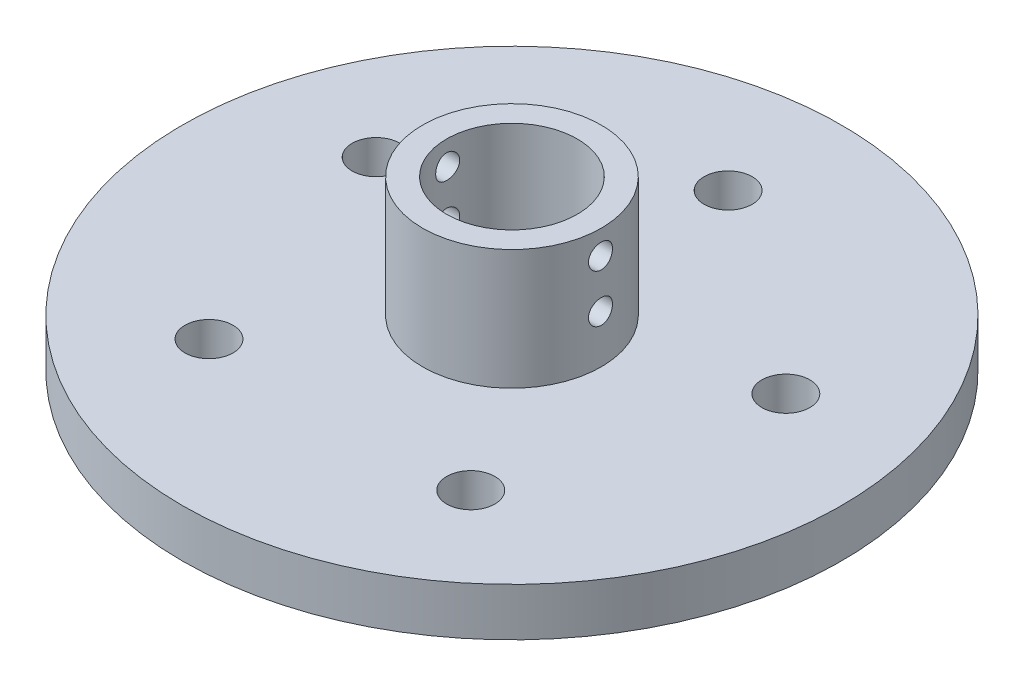
SolidWorks part; units mm, degrees
material "Delrin 2700 NC010, Low Viscosity Acetal Copolymer (SS)"
ref_plane "Front Plane" through (0, 0, 0) normal (0, 0, 1) x (1, 0, 0)
ref_plane "Top Plane" through (0, 0, 0) normal (0, 1, 0) x (1, 0, 0)
ref_plane "Right Plane" through (0, 0, 0) normal (1, 0, 0) x (0, 0, -1)
sketch "Sketch1" plane through (0, 0, 0) normal (0, 0, 1) x (1, 0, 0)
  line L0 (0, 7.8095) -> (0, 0) construction
  line L1 (0, 0) -> (17.272, 0) construction
  line L3 (17.272, 0) -> (87.122, 0)
  line L4 (17.272, 0) -> (17.272, 12.7)
  line L5 (17.272, 12.7) -> (87.122, 12.7)
  line L6 (87.122, 0) -> (87.122, 12.7)
  line L7 (17.272, 12.7) -> (23.622, 12.7)
  line L8 (17.272, 12.7) -> (17.272, 44.45)
  line L9 (17.272, 44.45) -> (23.622, 44.45)
  line L10 (23.622, 12.7) -> (23.622, 44.45)
  dimension "D1" = 17.272
  dimension "D2" = 12.7
  dimension "D3" = 6.35
  dimension "D4" = 31.75
  dimension "5.5" = 69.85
revolve "Revolve1" add sketch "Sketch1" angle 360 about L0 region at (52.197, 6.35, 0) region at (20.447, 28.575, 0)
sketch "Sketch2" plane through (0, 12.7, 0) normal (0, 1, 0) x (1, 0, 0)
  line L0 (0, 57.15) -> (54.1556, 18.2562) construction
  line L1 (54.1556, 18.2562) -> (34.5994, -45.4863) construction
  line L2 (34.5994, -45.4863) -> (-34.5994, -45.4863) construction
  line L3 (-34.5994, -45.4863) -> (-54.1556, 18.2562) construction
  line L4 (-54.1556, 18.2562) -> (0, 57.15) construction
  circle A0 centre (0, 0) radius 57.15 construction
  point P3 (-54.1556, 18.2562)
  point P4 (0, 57.15)
  point P5 (54.1556, 18.2562)
  point P6 (-34.5994, -45.4863)
  point P7 (34.5994, -45.4863)
  dimension "D1" = 114.3
  dimension "D2" = 66.675
hole_wizard "1/2-20 Tapped Hole1" positions "Sketch3" profile "Sketch4" tap size "1/2-20" standard "ANSI Inch" end condition through all
sketch "Sketch3" plane through (0, 12.7, 0) normal (0, 1, 0) x (1, 0, 0)
  point P0 (-54.1556, 18.2562)
  point P3 (0, 57.15)
  point P6 (54.1556, 18.2562)
  point P9 (34.5994, -45.4863)
  point P12 (-34.5994, -45.4863)
sketch "Sketch4" plane through (-54.1556, 12.7, -18.2562) normal (1, 0, 0) x (0, 0, 1)
  line L0 (0, 0) -> (0, 12.7)
  line L1 (0, 12.7) -> (6.35, 12.7)
  line L2 (6.35, 12.7) -> (6.35, 0)
  line L5 (6.35, 0) -> (0, 0)
  line L11 (0, -6.35) -> (0, 107.95) construction
  dimension "Thru Tap Drill Dia." = 12.7
  dimension "Thru Tap Drill Depth" = 12.7
cosmetic thread "Hole Thread1" parameters "D2"=12.7
cosmetic thread "Hole Thread2" parameters "D2"=12.7
cosmetic thread "Hole Thread4" parameters "D2"=12.7
cosmetic thread "Hole Thread5" parameters "D2"=12.7
cosmetic thread "Hole Thread6" parameters "D2"=12.7
hole_wizard "1/4 (0.25) Diameter Hole1" positions "Sketch6" profile "Sketch7" hole size "1/4" standard "ANSI Inch" end condition through all
sketch "Sketch6" plane through (0, 0, 0) normal (1, 0, 0) x (0, 0, -1)
  point P0 (0, 38.1)
  point P5 (0, 25.4)
  dimension "D1" = 38.1
  dimension "D2" = 25.4
sketch "Sketch7" plane through (0, 38.1, 0) normal (0, 1, 0) x (0, 0, 1)
  line L0 (0, 0) -> (0, 87.122)
  line L1 (0, 87.122) -> (3.175, 87.122)
  line L2 (3.175, 87.122) -> (3.175, 0)
  line L5 (3.175, 0) -> (0, 0)
  line L11 (0, -6.35) -> (0, 107.95) construction
  dimension "Thru Hole Dia." = 6.35
  dimension "Thru Hole Depth" = 87.122
hole_wizard "1/4 (0.25) Diameter Hole2" positions "Sketch8" profile "Sketch9" hole size "1/4" standard "ANSI Inch" end condition through all
sketch "Sketch8" plane through (0, 0, 0) normal (1, 0, 0) x (0, 0, -1)
  point P3 (0, 38.1)
  point P6 (0, 25.4)
sketch "Sketch9" plane through (0, 38.1, 0) normal (0, 1, 0) x (0, 0, -1)
  line L0 (0, 0) -> (0, 87.122)
  line L1 (0, 87.122) -> (3.175, 87.122)
  line L2 (3.175, 87.122) -> (3.175, 0)
  line L5 (3.175, 0) -> (0, 0)
  line L11 (0, -6.35) -> (0, 107.95) construction
  dimension "Thru Hole Dia." = 6.35
  dimension "Thru Hole Depth" = 87.122
